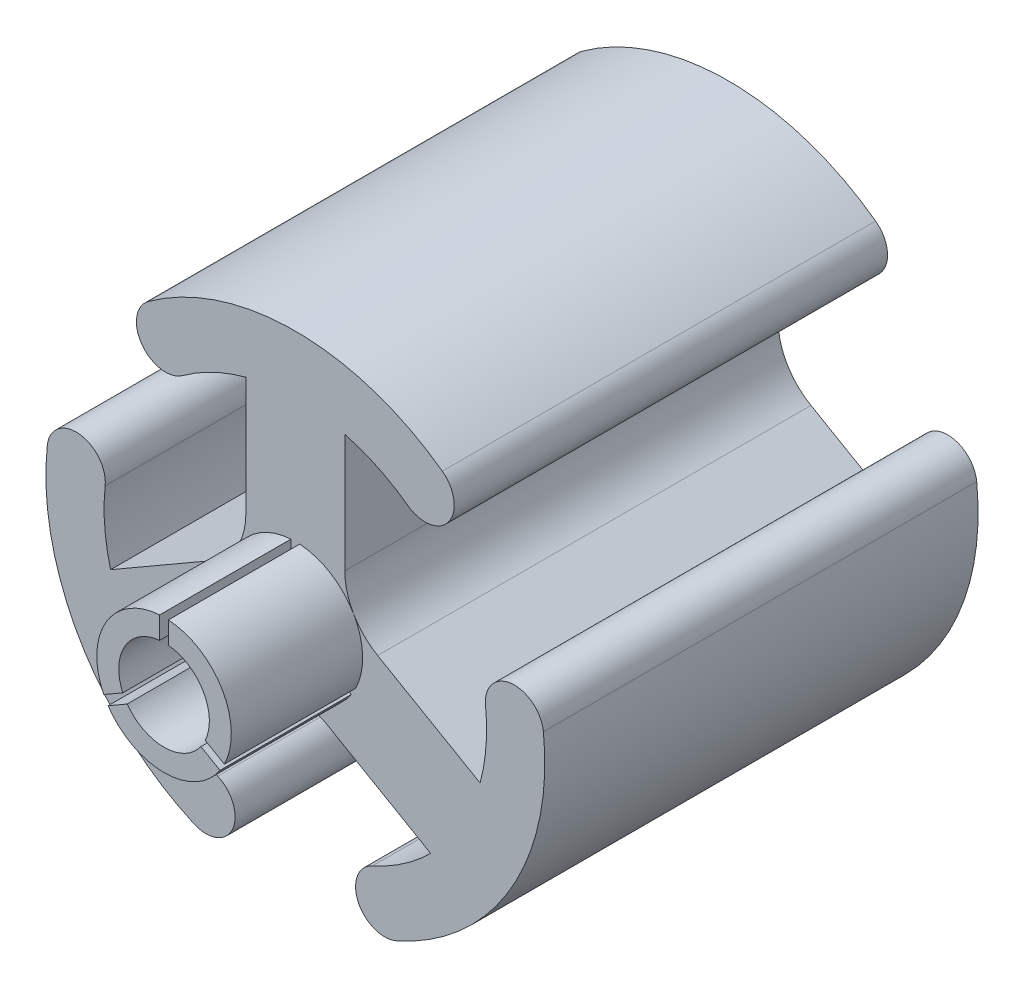
SolidWorks part; units mm, degrees
ref_plane "Front Plane" through (0, 0, 0) normal (0, 0, 1) x (1, 0, 0)
ref_plane "Top Plane" through (0, 0, 0) normal (0, 1, 0) x (1, 0, 0)
ref_plane "Right Plane" through (0, 0, 0) normal (1, 0, 0) x (0, 0, -1)
sketch "Sketch2" plane through (0, 0, 0) normal (0, 0, 1) x (1, 0, 0)
  line L0 (0, 19) -> (-16.4545, -9.5)
  line L1 (-16.4545, -9.5) -> (16.4545, -9.5)
  line L2 (16.4545, -9.5) -> (0, 19)
  line L9 (-3.7671, 0) -> (3.7671, 0)
  line L10 (-3.7671, 0) -> (-3.7671, 19)
  line L11 (-3.7671, 19) -> (3.7671, 19)
  line L12 (3.7671, 0) -> (3.7671, 19)
  circle A5 centre (0, 0) radius 19
  arc A6 (9.8862, 13.5628) -> (-9.8862, 13.5628) centre (0, 0) ccw construction
  arc A7 (11.1917, 15.354) -> (-11.1917, 15.354) centre (0, 0) ccw
  arc A8 (8.5806, 11.7717) -> (-8.5806, 11.7717) centre (0, 0) ccw
  arc A9 (8.5806, 11.7717) -> (11.1917, 15.354) centre (9.8862, 13.5628) ccw
  arc A10 (-11.1917, 15.354) -> (-8.5806, 11.7717) centre (-9.8862, 13.5628) ccw
  point P8 (0, 16.7835)
  dimension "D1" = 38
extrude "Boss-Extrude3" add sketch "Sketch2" against normal blind 33 contours L12 A8 L10 L9 | L12 A8 L2 | L0 A8 L10 | A9 A7 A10 A8 region at (0, 7.0995, 0) region at (-3.4118, 13.6251, 0) region at (3.4118, 13.6251, 0)
sketch "Sketch5" plane through (0, 0, 0) normal (1, 0, 0) x (0, 0, -1)
  line L0 (0, 0) -> (12.727, 0)
pattern_circular "CirPattern1" count 3 over 360 about axis through (0, 0, 0) along (0, 0, -1) of "Boss-Extrude3"
fillet "Fillet1" radius 5 3 edges at (3.7671, 2.1749, -16.5) (0, -4.3499, -16.5) (-3.7671, 2.1749, -16.5)
sketch "Sketch7" plane through (0, 0, 0) normal (0, 0, 1) x (1, 0, 0)
  line L0 (0.9246, -0.9165) -> (1.2561, -0.3425)
  line L1 (0.3314, 1.259) -> (-0.3314, 1.259)
  line L2 (0.3314, 1.259) -> (0.3314, 5.1234)
  line L3 (0.3314, 5.1234) -> (-0.3314, 5.1234)
  line L4 (-0.3314, 1.259) -> (-0.3314, 5.1234)
  line L5 (1.2561, -0.3425) -> (4.6027, -2.2747)
  line L6 (0.9246, -0.9165) -> (4.2713, -2.8487)
  line L7 (4.2713, -2.8487) -> (4.6027, -2.2747)
  line L8 (-1.2561, -0.3425) -> (-0.9246, -0.9165)
  line L9 (-0.9246, -0.9165) -> (-4.2713, -2.8487)
  line L10 (-1.2561, -0.3425) -> (-4.6027, -2.2747)
  line L11 (-4.6027, -2.2747) -> (-4.2713, -2.8487)
  circle A0 centre (0, 0) radius 5.1234
  point P7 (0, 1.259)
  point P18 (0, 0)
  dimension "D1" = 3
extrude "Boss-Extrude4" add sketch "Sketch7" along normal blind 10 contours L4 A0 L10 L8 L9 L6 L0 L5 L2 L1 region at (0, 0, 0)
sketch "Sketch6" plane through (0, 0, -33) normal (0, 0, -1) x (-1, 0, 0)
  circle A0 centre (0, 0) radius 3.45
extrude "Cut-Extrude1" cut sketch "Sketch6" against normal blind 50
